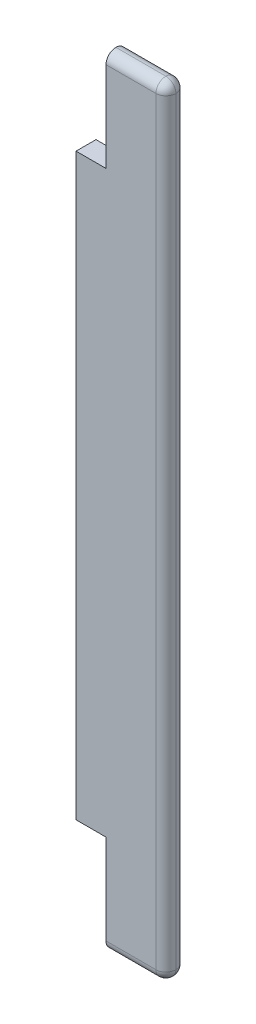
SolidWorks part; units mm, degrees
ref_plane "Front Plane" through (0, 0, 0) normal (0, 0, 1) x (1, 0, 0)
ref_plane "Top Plane" through (0, 0, 0) normal (0, 1, 0) x (1, 0, 0)
ref_plane "Right Plane" through (0, 0, 0) normal (1, 0, 0) x (0, 0, -1)
sketch "Sketch1" plane through (0, 0, 0) normal (0, 0, 1) x (1, 0, 0)
  line L0 (-40, -120.1726) -> (-40, 169.8274)
  line L1 (-40, 169.8274) -> (-25, 169.8274)
  line L2 (-25, 169.8274) -> (-25, 219.8274)
  line L3 (-25, 219.8274) -> (5, 219.8274)
  line L4 (5, 219.8274) -> (5, -170.1726)
  line L5 (5, -170.1726) -> (-25, -170.1726)
  line L6 (-25, -170.1726) -> (-25, -120.1726)
  line L7 (-25, -120.1726) -> (-40, -120.1726)
  point P10 (-40, 24.8274)
  dimension "D1" = 390
  dimension "D2" = 145
  dimension "D3" = 145
  dimension "D4" = 30
  dimension "D5" = 15
  dimension "D6" = 30
  dimension "D7" = 15
extrude "Boss-Extrude1" add sketch "Sketch1" along normal blind 10
fillet "Fillet1" radius 5 4 edges at (5, -170.1726, 5) (5, 24.8274, 10) (5, 219.8274, 5) (5, 24.8274, 0)
fillet "Fillet2" radius 5 4 edges at (3.5355, -168.7082, 1.4645) (3.5355, -168.7082, 8.5355) (-12.5, -170.1726, 0) (-12.5, -170.1726, 10)
fillet "Fillet3" radius 5 4 edges at (3.5355, 218.3629, 1.4645) (3.5355, 218.3629, 8.5355) (-12.5, 219.8274, 0) (-12.5, 219.8274, 10)
